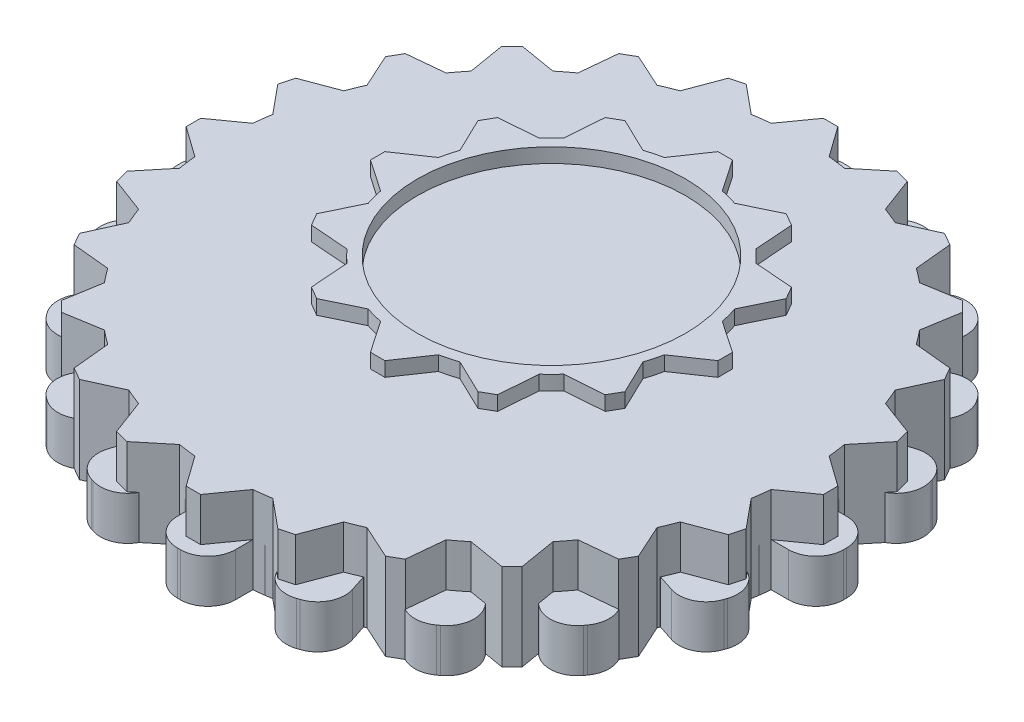
SolidWorks part; units mm, degrees
ref_plane "Front Plane" through (0, 0, 0) normal (0, 0, 1) x (1, 0, 0)
ref_plane "Top Plane" through (0, 0, 0) normal (0, 1, 0) x (1, 0, 0)
ref_plane "Right Plane" through (0, 0, 0) normal (1, 0, 0) x (0, 0, -1)
sketch "Sketch1" plane through (0, 0, 0) normal (0, 1, 0) x (1, 0, 0)
  line L86 (-2.6424, 4.8669) -> (1.3576, 4.8669)
  line L111 (-1.1424, 15.3669) -> (-0.1424, 15.3669)
  line L112 (-0.1424, 15.3669) -> (1.3576, 13.1649)
  line L113 (-1.1424, 15.3669) -> (-2.6424, 13.1649)
  line L114 (5.7906, 13.5092) -> (5.9886, 10.8522)
  line L115 (4.9246, 14.0092) -> (5.7906, 13.5092)
  line L116 (4.9246, 14.0092) -> (2.5245, 12.8522)
  line L117 (9.9999, 8.9339) -> (8.8429, 6.5338)
  line L118 (9.4999, 9.7999) -> (9.9999, 8.9339)
  line L119 (9.4999, 9.7999) -> (6.8429, 9.9979)
  line L120 (11.3576, 2.8669) -> (9.1556, 1.3669)
  line L121 (11.3576, 3.8669) -> (11.3576, 2.8669)
  line L122 (11.3576, 3.8669) -> (9.1556, 5.3669)
  line L123 (9.4999, -3.0661) -> (6.8429, -3.2641)
  line L124 (9.9999, -2.2001) -> (9.4999, -3.0661)
  line L125 (9.9999, -2.2001) -> (8.8429, 0.2)
  line L126 (4.9246, -7.2754) -> (2.5245, -6.1184)
  line L127 (5.7906, -6.7754) -> (4.9246, -7.2754)
  line L128 (5.7906, -6.7754) -> (5.9886, -4.1184)
  line L129 (-1.1424, -8.6331) -> (-2.6424, -6.4311)
  line L130 (-0.1424, -8.6331) -> (-1.1424, -8.6331)
  line L131 (-0.1424, -8.6331) -> (1.3576, -6.4311)
  line L132 (-7.0754, -6.7754) -> (-7.2734, -4.1184)
  line L133 (-6.2094, -7.2754) -> (-7.0754, -6.7754)
  line L134 (-6.2094, -7.2754) -> (-3.8093, -6.1184)
  line L135 (-11.2847, -2.2001) -> (-10.1277, 0.2)
  line L136 (-10.7847, -3.0661) -> (-11.2847, -2.2001)
  line L137 (-10.7847, -3.0661) -> (-8.1277, -3.2641)
  line L138 (-12.6424, 3.8669) -> (-10.4404, 5.3669)
  line L139 (-12.6424, 2.8669) -> (-12.6424, 3.8669)
  line L140 (-12.6424, 2.8669) -> (-10.4404, 1.3669)
  line L141 (-10.7847, 9.7999) -> (-8.1277, 9.9979)
  line L142 (-11.2847, 8.9339) -> (-10.7847, 9.7999)
  line L143 (-11.2847, 8.9339) -> (-10.1277, 6.5338)
  line L144 (-6.2094, 14.0092) -> (-3.8093, 12.8522)
  line L145 (-7.0754, 13.5092) -> (-6.2094, 14.0092)
  line L146 (-7.0754, 13.5092) -> (-7.2734, 10.8522)
  line L147 (-2.6424, 1.8669) -> (1.3576, 1.8669)
  line L149 (-3.1424, 4.8669) -> (1.8576, 1.8669) construction
  line L150 (-3.1424, 1.8669) -> (1.8576, 4.8669) construction
  arc A43 (-2.6424, 13.1649) -> (-3.8093, 12.8522) centre (-0.6424, 3.3669) ccw
  arc A44 (-7.2734, 10.8522) -> (-8.1277, 9.9979) centre (-0.6424, 3.3669) ccw
  arc A45 (-10.1277, 6.5338) -> (-10.4404, 5.3669) centre (-0.6424, 3.3669) ccw
  arc A46 (-10.4404, 1.3669) -> (-10.1277, 0.2) centre (-0.6424, 3.3669) ccw
  arc A47 (-8.1277, -3.2641) -> (-7.2734, -4.1184) centre (-0.6424, 3.3669) ccw
  arc A48 (-3.8093, -6.1184) -> (-2.6424, -6.4311) centre (-0.6424, 3.3669) ccw
  arc A49 (1.3576, -6.4311) -> (2.5245, -6.1184) centre (-0.6424, 3.3669) ccw
  arc A50 (5.9886, -4.1184) -> (6.8429, -3.2641) centre (-0.6424, 3.3669) ccw
  arc A51 (8.8429, 0.2) -> (9.1556, 1.3669) centre (-0.6424, 3.3669) ccw
  arc A52 (9.1556, 5.3669) -> (8.8429, 6.5338) centre (-0.6424, 3.3669) ccw
  arc A53 (6.8429, 9.9979) -> (5.9886, 10.8522) centre (-0.6424, 3.3669) ccw
  arc A54 (2.5245, 12.8522) -> (1.3576, 13.1649) centre (-0.6424, 3.3669) ccw
  arc A55 (-2.6424, 4.8669) -> (-2.6424, 1.8669) centre (-0.6424, 3.3669) ccw
  arc A56 (1.3576, 1.8669) -> (1.3576, 4.8669) centre (-0.6424, 3.3669) ccw
  point P6 (0, 0)
  point P8 (0, 0)
  point P9 (0, 0)
  point P12 (0, 2.7462)
  point P17 (0, 0)
  point P18 (0, 2.7462)
  point P22 (-2.5, 0.7462)
  point P63 (0, 0)
  point P68 (0, 0)
  point P69 (-0.6424, 3.3669)
  point P119 (0, 0)
  dimension "D1" = 20
  dimension "D2" = 3
  dimension "D3" = 5
  dimension "D8" = 12
sketch "Sketch2" plane through (0, 0, 0) normal (0, 1, 0) x (1, 0, 0)
  line L0 (-2, 0) -> (2, 0)
  line L1 (-23, -0.1) -> (-23, 0.1)
  line L2 (-21.1, 2) -> (-19.8997, 2)
  line L3 (-21.1, -2) -> (-19.8997, -2)
  line L4 (-20.6853, 4.6181) -> (-19.5438, 4.2472)
  line L5 (-19.4493, 8.4224) -> (-18.3078, 8.0515)
  line L6 (-21.9052, 7.0123) -> (-21.8434, 7.2025)
  line L7 (-18.2458, 10.7842) -> (-17.2748, 10.0787)
  line L8 (-15.8947, 14.0203) -> (-14.9237, 13.3148)
  line L9 (-18.6662, 13.4382) -> (-18.5486, 13.6)
  line L10 (-14.0203, 15.8947) -> (-13.3148, 14.9237)
  line L11 (-10.7842, 18.2458) -> (-10.0787, 17.2748)
  line L12 (-13.6, 18.5486) -> (-13.4382, 18.6662)
  line L13 (-8.4224, 19.4493) -> (-8.0515, 18.3078)
  line L14 (-4.6181, 20.6853) -> (-4.2472, 19.5438)
  line L15 (-7.2025, 21.8434) -> (-7.0123, 21.9052)
  line L16 (-2, 21.1) -> (-2, 19.8997)
  line L17 (2, 21.1) -> (2, 19.8997)
  line L18 (-0.1, 23) -> (0.1, 23)
  line L19 (4.6181, 20.6853) -> (4.2472, 19.5438)
  line L20 (8.4224, 19.4493) -> (8.0515, 18.3078)
  line L21 (7.0123, 21.9052) -> (7.2025, 21.8434)
  line L22 (10.7842, 18.2458) -> (10.0787, 17.2748)
  line L23 (14.0203, 15.8947) -> (13.3148, 14.9237)
  line L24 (13.4382, 18.6662) -> (13.6, 18.5486)
  line L25 (15.8947, 14.0203) -> (14.9237, 13.3148)
  line L26 (18.2458, 10.7842) -> (17.2748, 10.0787)
  line L27 (18.5486, 13.6) -> (18.6662, 13.4382)
  line L28 (19.4493, 8.4224) -> (18.3078, 8.0515)
  line L29 (20.6853, 4.6181) -> (19.5438, 4.2472)
  line L30 (21.8434, 7.2025) -> (21.9052, 7.0123)
  line L31 (21.1, 2) -> (19.8997, 2)
  line L32 (21.1, -2) -> (19.8997, -2)
  line L33 (23, 0.1) -> (23, -0.1)
  line L34 (20.6853, -4.6181) -> (19.5438, -4.2472)
  line L35 (19.4493, -8.4224) -> (18.3078, -8.0515)
  line L36 (21.9052, -7.0123) -> (21.8434, -7.2025)
  line L37 (18.2458, -10.7842) -> (17.2748, -10.0787)
  line L38 (15.8947, -14.0203) -> (14.9237, -13.3148)
  line L39 (18.6662, -13.4382) -> (18.5486, -13.6)
  line L40 (14.0203, -15.8947) -> (13.3148, -14.9237)
  line L41 (10.7842, -18.2458) -> (10.0787, -17.2748)
  line L42 (13.6, -18.5486) -> (13.4382, -18.6662)
  line L43 (8.4224, -19.4493) -> (8.0515, -18.3078)
  line L44 (4.6181, -20.6853) -> (4.2472, -19.5438)
  line L45 (7.2025, -21.8434) -> (7.0123, -21.9052)
  line L46 (2, -21.1) -> (2, -19.8997)
  line L47 (-2, -21.1) -> (-2, -19.8997)
  line L48 (0.1, -23) -> (-0.1, -23)
  line L49 (-4.6181, -20.6853) -> (-4.2472, -19.5438)
  line L50 (-8.4224, -19.4493) -> (-8.0515, -18.3078)
  line L51 (-7.0123, -21.9052) -> (-7.2025, -21.8434)
  line L52 (-10.7842, -18.2458) -> (-10.0787, -17.2748)
  line L53 (-14.0203, -15.8947) -> (-13.3148, -14.9237)
  line L54 (-13.4382, -18.6662) -> (-13.6, -18.5486)
  line L55 (-15.8947, -14.0203) -> (-14.9237, -13.3148)
  line L56 (-18.2458, -10.7842) -> (-17.2748, -10.0787)
  line L57 (-18.5486, -13.6) -> (-18.6662, -13.4382)
  line L58 (-19.4493, -8.4224) -> (-18.3078, -8.0515)
  line L59 (-20.6853, -4.6181) -> (-19.5438, -4.2472)
  line L60 (-21.8434, -7.2025) -> (-21.9052, -7.0123)
  arc A0 (-18.3078, -8.0515) -> (-17.2748, -10.0787) centre (0, 0) ccw
  arc A1 (-21.1, 2) -> (-23, 0.1) centre (-21.1, 0.1) ccw
  arc A2 (-21.1, -2) -> (-23, -0.1) centre (-21.1, -0.1) cw
  arc A3 (-20.6853, 4.6181) -> (-21.9052, 7.0123) centre (-20.0982, 6.4252) cw
  arc A4 (-19.4493, 8.4224) -> (-21.8434, 7.2025) centre (-20.0364, 6.6154) ccw
  arc A5 (-18.2458, 10.7842) -> (-18.6662, 13.4382) centre (-17.129, 12.3214) cw
  arc A6 (-15.8947, 14.0203) -> (-18.5486, 13.6) centre (-17.0115, 12.4832) ccw
  arc A7 (-14.0203, 15.8947) -> (-13.6, 18.5486) centre (-12.4832, 17.0115) cw
  arc A8 (-10.7842, 18.2458) -> (-13.4382, 18.6662) centre (-12.3214, 17.129) ccw
  arc A9 (-8.4224, 19.4493) -> (-7.2025, 21.8434) centre (-6.6154, 20.0364) cw
  arc A10 (-4.6181, 20.6853) -> (-7.0123, 21.9052) centre (-6.4252, 20.0982) ccw
  arc A11 (-2, 21.1) -> (-0.1, 23) centre (-0.1, 21.1) cw
  arc A12 (2, 21.1) -> (0.1, 23) centre (0.1, 21.1) ccw
  arc A13 (4.6181, 20.6853) -> (7.0123, 21.9052) centre (6.4252, 20.0982) cw
  arc A14 (8.4224, 19.4493) -> (7.2025, 21.8434) centre (6.6154, 20.0364) ccw
  arc A15 (10.7842, 18.2458) -> (13.4382, 18.6662) centre (12.3214, 17.129) cw
  arc A16 (14.0203, 15.8947) -> (13.6, 18.5486) centre (12.4832, 17.0115) ccw
  arc A17 (15.8947, 14.0203) -> (18.5486, 13.6) centre (17.0115, 12.4832) cw
  arc A18 (18.2458, 10.7842) -> (18.6662, 13.4382) centre (17.129, 12.3214) ccw
  arc A19 (19.4493, 8.4224) -> (21.8434, 7.2025) centre (20.0364, 6.6154) cw
  arc A20 (20.6853, 4.6181) -> (21.9052, 7.0123) centre (20.0982, 6.4252) ccw
  arc A21 (21.1, 2) -> (23, 0.1) centre (21.1, 0.1) cw
  arc A22 (21.1, -2) -> (23, -0.1) centre (21.1, -0.1) ccw
  arc A23 (20.6853, -4.6181) -> (21.9052, -7.0123) centre (20.0982, -6.4252) cw
  arc A24 (19.4493, -8.4224) -> (21.8434, -7.2025) centre (20.0364, -6.6154) ccw
  arc A25 (18.2458, -10.7842) -> (18.6662, -13.4382) centre (17.129, -12.3214) cw
  arc A26 (15.8947, -14.0203) -> (18.5486, -13.6) centre (17.0115, -12.4832) ccw
  arc A27 (14.0203, -15.8947) -> (13.6, -18.5486) centre (12.4832, -17.0115) cw
  arc A28 (10.7842, -18.2458) -> (13.4382, -18.6662) centre (12.3214, -17.129) ccw
  arc A29 (8.4224, -19.4493) -> (7.2025, -21.8434) centre (6.6154, -20.0364) cw
  arc A30 (4.6181, -20.6853) -> (7.0123, -21.9052) centre (6.4252, -20.0982) ccw
  arc A31 (2, -21.1) -> (0.1, -23) centre (0.1, -21.1) cw
  arc A32 (-2, -21.1) -> (-0.1, -23) centre (-0.1, -21.1) ccw
  arc A33 (-4.6181, -20.6853) -> (-7.0123, -21.9052) centre (-6.4252, -20.0982) cw
  arc A34 (-8.4224, -19.4493) -> (-7.2025, -21.8434) centre (-6.6154, -20.0364) ccw
  arc A35 (-10.7842, -18.2458) -> (-13.4382, -18.6662) centre (-12.3214, -17.129) cw
  arc A36 (-14.0203, -15.8947) -> (-13.6, -18.5486) centre (-12.4832, -17.0115) ccw
  arc A37 (-15.8947, -14.0203) -> (-18.5486, -13.6) centre (-17.0115, -12.4832) cw
  arc A38 (-18.2458, -10.7842) -> (-18.6662, -13.4382) centre (-17.129, -12.3214) ccw
  arc A39 (-19.4493, -8.4224) -> (-21.8434, -7.2025) centre (-20.0364, -6.6154) cw
  arc A40 (-20.6853, -4.6181) -> (-21.9052, -7.0123) centre (-20.0982, -6.4252) ccw
  arc A41 (-19.8997, -2) -> (-19.5438, -4.2472) centre (0, 0) ccw
  arc A42 (-19.5438, 4.2472) -> (-19.8997, 2) centre (0, 0) ccw
  arc A43 (-17.2748, 10.0787) -> (-18.3078, 8.0515) centre (0, 0) ccw
  arc A44 (-13.3148, 14.9237) -> (-14.9237, 13.3148) centre (0, 0) ccw
  arc A45 (-8.0515, 18.3078) -> (-10.0787, 17.2748) centre (0, 0) ccw
  arc A46 (-2, 19.8997) -> (-4.2472, 19.5438) centre (0, 0) ccw
  arc A47 (4.2472, 19.5438) -> (2, 19.8997) centre (0, 0) ccw
  arc A48 (10.0787, 17.2748) -> (8.0515, 18.3078) centre (0, 0) ccw
  arc A49 (14.9237, 13.3148) -> (13.3148, 14.9237) centre (0, 0) ccw
  arc A50 (18.3078, 8.0515) -> (17.2748, 10.0787) centre (0, 0) ccw
  arc A51 (19.8997, 2) -> (19.5438, 4.2472) centre (0, 0) ccw
  arc A52 (19.5438, -4.2472) -> (19.8997, -2) centre (0, 0) ccw
  arc A53 (17.2748, -10.0787) -> (18.3078, -8.0515) centre (0, 0) ccw
  arc A54 (13.3148, -14.9237) -> (14.9237, -13.3148) centre (0, 0) ccw
  arc A55 (8.0515, -18.3078) -> (10.0787, -17.2748) centre (0, 0) ccw
  arc A56 (2, -19.8997) -> (4.2472, -19.5438) centre (0, 0) ccw
  arc A57 (-10.0787, -17.2748) -> (-8.0515, -18.3078) centre (0, 0) ccw
  arc A58 (-4.2472, -19.5438) -> (-2, -19.8997) centre (0, 0) ccw
  arc A59 (-14.9237, -13.3148) -> (-13.3148, -14.9237) centre (0, 0) ccw
  point P6 (0, 0)
  point P10 (-23, 2)
  point P170 (0, 0)
  dimension "D1" = 40
  dimension "D4" = 1.9
  dimension "D5" = 20
extrude "Boss-Extrude3" add sketch "Sketch2" along normal blind 3 contours L55 A59 L53 A36 L54 A35 L52 A57 L50 A34 L51 A33 L49 A58 L47 A32 L48 A31 L46 A56 L44 A30 L45 A29 L43 A55 L41 A28 L42 A27 L40 A54 L38 A26 L39 A25 L37 A53 L35 A24 L36 A23 L34 A52 L32 A22 L33 A21 region at (-22.3495, 0, 0)
sketch "Sketch3" plane through (0, 0, 0) normal (0, 1, 0) x (1, 0, 0)
  line L0 (-22, 0) -> (22, 0)
  line L1 (22, -0.5) -> (22, 0.5)
  line L2 (22, 0.5) -> (19.8997, 2)
  line L3 (22, -0.5) -> (19.8997, -2)
  line L4 (21.3798, -5.2111) -> (19.7393, -3.2186)
  line L5 (21.121, -6.177) -> (21.3798, -5.2111)
  line L6 (21.121, -6.177) -> (18.704, -7.0823)
  line L7 (19.3026, -10.567) -> (18.2337, -8.2178)
  line L8 (18.8026, -11.433) -> (19.3026, -10.567)
  line L9 (18.8026, -11.433) -> (16.2337, -11.6819)
  line L10 (15.9099, -15.2028) -> (15.4855, -12.657)
  line L11 (15.2028, -15.9099) -> (15.9099, -15.2028)
  line L12 (15.2028, -15.9099) -> (12.657, -15.4855)
  line L13 (11.433, -18.8026) -> (11.6819, -16.2337)
  line L14 (10.567, -19.3026) -> (11.433, -18.8026)
  line L15 (10.567, -19.3026) -> (8.2178, -18.2337)
  line L16 (6.177, -21.121) -> (7.0823, -18.704)
  line L17 (5.2111, -21.3798) -> (6.177, -21.121)
  line L18 (5.2111, -21.3798) -> (3.2186, -19.7393)
  line L19 (0.5, -22) -> (2, -19.8997)
  line L20 (-0.5, -22) -> (0.5, -22)
  line L21 (-0.5, -22) -> (-2, -19.8997)
  line L22 (-5.2111, -21.3798) -> (-3.2186, -19.7393)
  line L23 (-6.177, -21.121) -> (-5.2111, -21.3798)
  line L24 (-6.177, -21.121) -> (-7.0823, -18.704)
  line L25 (-10.567, -19.3026) -> (-8.2178, -18.2337)
  line L26 (-11.433, -18.8026) -> (-10.567, -19.3026)
  line L27 (-11.433, -18.8026) -> (-11.6819, -16.2337)
  line L28 (-15.2028, -15.9099) -> (-12.657, -15.4855)
  line L29 (-15.9099, -15.2028) -> (-15.2028, -15.9099)
  line L30 (-15.9099, -15.2028) -> (-15.4855, -12.657)
  line L31 (-18.8026, -11.433) -> (-16.2337, -11.6819)
  line L32 (-19.3026, -10.567) -> (-18.8026, -11.433)
  line L33 (-19.3026, -10.567) -> (-18.2337, -8.2178)
  line L34 (-21.121, -6.177) -> (-18.704, -7.0823)
  line L35 (-21.3798, -5.2111) -> (-21.121, -6.177)
  line L36 (-21.3798, -5.2111) -> (-19.7393, -3.2186)
  line L37 (-22, -0.5) -> (-19.8997, -2)
  line L38 (-22, 0.5) -> (-22, -0.5)
  line L39 (-22, 0.5) -> (-19.8997, 2)
  line L40 (-21.3798, 5.2111) -> (-19.7393, 3.2186)
  line L41 (-21.121, 6.177) -> (-21.3798, 5.2111)
  line L42 (-21.121, 6.177) -> (-18.704, 7.0823)
  line L43 (-19.3026, 10.567) -> (-18.2337, 8.2178)
  line L44 (-18.8026, 11.433) -> (-19.3026, 10.567)
  line L45 (-18.8026, 11.433) -> (-16.2337, 11.6819)
  line L46 (-15.9099, 15.2028) -> (-15.4855, 12.657)
  line L47 (-15.2028, 15.9099) -> (-15.9099, 15.2028)
  line L48 (-15.2028, 15.9099) -> (-12.657, 15.4855)
  line L49 (-11.433, 18.8026) -> (-11.6819, 16.2337)
  line L50 (-10.567, 19.3026) -> (-11.433, 18.8026)
  line L51 (-10.567, 19.3026) -> (-8.2178, 18.2337)
  line L52 (-6.177, 21.121) -> (-7.0823, 18.704)
  line L53 (-5.2111, 21.3798) -> (-6.177, 21.121)
  line L54 (-5.2111, 21.3798) -> (-3.2186, 19.7393)
  line L55 (-0.5, 22) -> (-2, 19.8997)
  line L56 (0.5, 22) -> (-0.5, 22)
  line L57 (0.5, 22) -> (2, 19.8997)
  line L58 (5.2111, 21.3798) -> (3.2186, 19.7393)
  line L59 (6.177, 21.121) -> (5.2111, 21.3798)
  line L60 (6.177, 21.121) -> (7.0823, 18.704)
  line L61 (10.567, 19.3026) -> (8.2178, 18.2337)
  line L62 (11.433, 18.8026) -> (10.567, 19.3026)
  line L63 (11.433, 18.8026) -> (11.6819, 16.2337)
  line L64 (15.2028, 15.9099) -> (12.657, 15.4855)
  line L65 (15.9099, 15.2028) -> (15.2028, 15.9099)
  line L66 (15.9099, 15.2028) -> (15.4855, 12.657)
  line L67 (18.8026, 11.433) -> (16.2337, 11.6819)
  line L68 (19.3026, 10.567) -> (18.8026, 11.433)
  line L69 (19.3026, 10.567) -> (18.2337, 8.2178)
  line L70 (21.121, 6.177) -> (18.704, 7.0823)
  line L71 (21.3798, 5.2111) -> (21.121, 6.177)
  line L72 (21.3798, 5.2111) -> (19.7393, 3.2186)
  arc A0 (-8.2178, -18.2337) -> (-7.0823, -18.704) centre (0, 0) ccw
  arc A1 (-12.657, -15.4855) -> (-11.6819, -16.2337) centre (0, 0) ccw
  arc A2 (-16.2337, -11.6819) -> (-15.4855, -12.657) centre (0, 0) ccw
  arc A3 (-18.704, -7.0823) -> (-18.2337, -8.2178) centre (0, 0) ccw
  arc A4 (-19.8997, -2) -> (-19.7393, -3.2186) centre (0, 0) ccw
  arc A5 (-19.7393, 3.2186) -> (-19.8997, 2) centre (0, 0) ccw
  arc A6 (-18.2337, 8.2178) -> (-18.704, 7.0823) centre (0, 0) ccw
  arc A7 (-15.4855, 12.657) -> (-16.2337, 11.6819) centre (0, 0) ccw
  arc A8 (-11.6819, 16.2337) -> (-12.657, 15.4855) centre (0, 0) ccw
  arc A9 (-7.0823, 18.704) -> (-8.2178, 18.2337) centre (0, 0) ccw
  arc A10 (-2, 19.8997) -> (-3.2186, 19.7393) centre (0, 0) ccw
  arc A11 (3.2186, 19.7393) -> (2, 19.8997) centre (0, 0) ccw
  arc A12 (8.2178, 18.2337) -> (7.0823, 18.704) centre (0, 0) ccw
  arc A13 (12.657, 15.4855) -> (11.6819, 16.2337) centre (0, 0) ccw
  arc A14 (16.2337, 11.6819) -> (15.4855, 12.657) centre (0, 0) ccw
  arc A15 (18.704, 7.0823) -> (18.2337, 8.2178) centre (0, 0) ccw
  arc A16 (19.8997, 2) -> (19.7393, 3.2186) centre (0, 0) ccw
  arc A17 (19.7393, -3.2186) -> (19.8997, -2) centre (0, 0) ccw
  arc A18 (18.2337, -8.2178) -> (18.704, -7.0823) centre (0, 0) ccw
  arc A19 (-3.2186, -19.7393) -> (-2, -19.8997) centre (0, 0) ccw
  arc A20 (2, -19.8997) -> (3.2186, -19.7393) centre (0, 0) ccw
  arc A21 (7.0823, -18.704) -> (8.2178, -18.2337) centre (0, 0) ccw
  arc A22 (11.6819, -16.2337) -> (12.657, -15.4855) centre (0, 0) ccw
  arc A23 (15.4855, -12.657) -> (16.2337, -11.6819) centre (0, 0) ccw
  point P6 (0, 0)
  point P7 (0, -12.952)
  point P8 (-6.2727, 0)
  point P9 (11.4668, 0)
  point P10 (0, 0)
  point P108 (0, 0)
  dimension "D1" = 40
  dimension "D2" = 22
  dimension "D3" = 2
  dimension "D4" = 24
extrude "Boss-Extrude5" add sketch "Sketch3" along normal blind 6 separate body contours L2 A16 L72 L71 L70 A15 L69 L68 L67 A14 L66 L65 L64 A13 L63 L62 L61 A12 L60 L59 L58 A11 L57 L56 L55 A10 L54 L53 L52 A9 L51 L50 L49 A8 L48 L47 L46 A7 L45 L44 L43 A6 L42 L41 L40 A5 L39 L38 L0 L1 | L10 A23 L9 L8 L7 A18 L6 L5 L4 A17 L3 L1 L0 L38 L37 A4 L36 L35 L34 A3 L33 L32 L31 A2 L30 L29 L28 A1 L27 L26 L25 A0 L24 L23 L22 A19 L21 L20 L19 A20 L18 L17 L16 A21 L15 L14 L13 A22 L12 L11 region at (0, 0, -8.8989) region at (0, 0, 8.8989)
extrude "Boss-Extrude6" add sketch "Sketch1" along normal blind 5.5 separate body
sketch "Sketch5" plane through (0, 5.5, 0) normal (0, 1, 0) x (1, 0, 0)
  line L0 (-0.6424, 15.3669) -> (-0.6424, -8.6331) construction
  line L1 (-0.1424, 15.3669) -> (-1.1424, 15.3669) construction
  line L2 (-1.1424, -8.6331) -> (-0.1424, -8.6331) construction
  line L3 (11.3576, 3.3669) -> (-12.6424, 3.3669) construction
  line L4 (11.3576, 2.8669) -> (11.3576, 3.8669) construction
  line L5 (-12.6424, 3.8669) -> (-12.6424, 2.8669) construction
  circle A0 centre (-0.6424, 3.3669) radius 5.1751
sketch "Sketch6" plane through (0, 5.5, 0) normal (0, 1, 0) x (1, 0, 0)
  line L72 (-1.1424, 15.3669) -> (-2.6424, 13.1649)
  line L73 (-3.8093, 12.8522) -> (-6.2094, 14.0092)
  line L74 (-6.2094, 14.0092) -> (-7.0754, 13.5092)
  line L75 (-7.0754, 13.5092) -> (-7.2734, 10.8522)
  line L76 (-8.1277, 9.9979) -> (-10.7847, 9.7999)
  line L77 (-10.7847, 9.7999) -> (-11.2847, 8.9339)
  line L78 (-11.2847, 8.9339) -> (-10.1277, 6.5338)
  line L79 (-10.4404, 5.3669) -> (-12.6424, 3.8669)
  line L80 (-12.6424, 3.8669) -> (-12.6424, 2.8669)
  line L81 (-12.6424, 2.8669) -> (-10.4404, 1.3669)
  line L82 (-10.1277, 0.2) -> (-11.2847, -2.2001)
  line L83 (-11.2847, -2.2001) -> (-10.7847, -3.0661)
  line L84 (-10.7847, -3.0661) -> (-8.1277, -3.2641)
  line L85 (-7.2734, -4.1184) -> (-7.0754, -6.7754)
  line L86 (-7.0754, -6.7754) -> (-6.2094, -7.2754)
  line L87 (-6.2094, -7.2754) -> (-3.8093, -6.1184)
  line L88 (-2.6424, -6.4311) -> (-1.1424, -8.6331)
  line L89 (-1.1424, -8.6331) -> (-0.1424, -8.6331)
  line L90 (-0.1424, -8.6331) -> (1.3576, -6.4311)
  line L91 (2.5245, -6.1184) -> (4.9246, -7.2754)
  line L92 (4.9246, -7.2754) -> (5.7906, -6.7754)
  line L93 (5.7906, -6.7754) -> (5.9886, -4.1184)
  line L94 (6.8429, -3.2641) -> (9.4999, -3.0661)
  line L95 (9.4999, -3.0661) -> (9.9999, -2.2001)
  line L96 (9.9999, -2.2001) -> (8.8429, 0.2)
  line L97 (9.1556, 1.3669) -> (11.3576, 2.8669)
  line L98 (11.3576, 2.8669) -> (11.3576, 3.8669)
  line L99 (11.3576, 3.8669) -> (9.1556, 5.3669)
  line L100 (8.8429, 6.5338) -> (9.9999, 8.9339)
  line L101 (9.9999, 8.9339) -> (9.4999, 9.7999)
  line L102 (9.4999, 9.7999) -> (6.8429, 9.9979)
  line L103 (5.9886, 10.8522) -> (5.7906, 13.5092)
  line L104 (5.7906, 13.5092) -> (4.9246, 14.0092)
  line L105 (4.9246, 14.0092) -> (2.5245, 12.8522)
  line L106 (1.3576, 13.1649) -> (-0.1424, 15.3669)
  line L107 (-0.1424, 15.3669) -> (-1.1424, 15.3669)
  line L108 (-1.1424, 15.3669) -> (-2.6424, 13.1649)
  line L109 (-3.8093, 12.8522) -> (-6.2094, 14.0092)
  line L110 (-6.2094, 14.0092) -> (-7.0754, 13.5092)
  line L111 (-7.0754, 13.5092) -> (-7.2734, 10.8522)
  line L112 (-8.1277, 9.9979) -> (-10.7847, 9.7999)
  line L113 (-10.7847, 9.7999) -> (-11.2847, 8.9339)
  line L114 (-11.2847, 8.9339) -> (-10.1277, 6.5338)
  line L115 (-10.4404, 5.3669) -> (-12.6424, 3.8669)
  line L116 (-12.6424, 3.8669) -> (-12.6424, 2.8669)
  line L117 (-12.6424, 2.8669) -> (-10.4404, 1.3669)
  line L118 (-10.1277, 0.2) -> (-11.2847, -2.2001)
  line L119 (-11.2847, -2.2001) -> (-10.7847, -3.0661)
  line L120 (-10.7847, -3.0661) -> (-8.1277, -3.2641)
  line L121 (-7.2734, -4.1184) -> (-7.0754, -6.7754)
  line L122 (-7.0754, -6.7754) -> (-6.2094, -7.2754)
  line L123 (-6.2094, -7.2754) -> (-3.8093, -6.1184)
  line L124 (-2.6424, -6.4311) -> (-1.1424, -8.6331)
  line L125 (-1.1424, -8.6331) -> (-0.1424, -8.6331)
  line L126 (-0.1424, -8.6331) -> (1.3576, -6.4311)
  line L127 (2.5245, -6.1184) -> (4.9246, -7.2754)
  line L128 (4.9246, -7.2754) -> (5.7906, -6.7754)
  line L129 (5.7906, -6.7754) -> (5.9886, -4.1184)
  line L130 (6.8429, -3.2641) -> (9.4999, -3.0661)
  line L131 (9.4999, -3.0661) -> (9.9999, -2.2001)
  line L132 (9.9999, -2.2001) -> (8.8429, 0.2)
  line L133 (9.1556, 1.3669) -> (11.3576, 2.8669)
  line L134 (11.3576, 2.8669) -> (11.3576, 3.8669)
  line L135 (11.3576, 3.8669) -> (9.1556, 5.3669)
  line L136 (8.8429, 6.5338) -> (9.9999, 8.9339)
  line L137 (9.9999, 8.9339) -> (9.4999, 9.7999)
  line L138 (9.4999, 9.7999) -> (6.8429, 9.9979)
  line L139 (5.9886, 10.8522) -> (5.7906, 13.5092)
  line L140 (5.7906, 13.5092) -> (4.9246, 14.0092)
  line L141 (4.9246, 14.0092) -> (2.5245, 12.8522)
  line L142 (1.3576, 13.1649) -> (-0.1424, 15.3669)
  line L143 (-0.1424, 15.3669) -> (-1.1424, 15.3669)
  circle A0 centre (-0.6424, 3.3669) radius 9.25
  arc A27 (-2.6424, 13.1649) -> (-3.8093, 12.8522) centre (-0.6424, 3.3669) ccw
  arc A28 (-7.2734, 10.8522) -> (-8.1277, 9.9979) centre (-0.6424, 3.3669) ccw
  arc A29 (-10.1277, 6.5338) -> (-10.4404, 5.3669) centre (-0.6424, 3.3669) ccw
  arc A30 (-10.4404, 1.3669) -> (-10.1277, 0.2) centre (-0.6424, 3.3669) ccw
  arc A31 (-8.1277, -3.2641) -> (-7.2734, -4.1184) centre (-0.6424, 3.3669) ccw
  arc A32 (-3.8093, -6.1184) -> (-2.6424, -6.4311) centre (-0.6424, 3.3669) ccw
  arc A33 (1.3576, -6.4311) -> (2.5245, -6.1184) centre (-0.6424, 3.3669) ccw
  arc A34 (5.9886, -4.1184) -> (6.8429, -3.2641) centre (-0.6424, 3.3669) ccw
  arc A35 (8.8429, 0.2) -> (9.1556, 1.3669) centre (-0.6424, 3.3669) ccw
  arc A36 (9.1556, 5.3669) -> (8.8429, 6.5338) centre (-0.6424, 3.3669) ccw
  arc A37 (6.8429, 9.9979) -> (5.9886, 10.8522) centre (-0.6424, 3.3669) ccw
  arc A38 (2.5245, 12.8522) -> (1.3576, 13.1649) centre (-0.6424, 3.3669) ccw
  arc A39 (-2.6424, 13.1649) -> (-3.8093, 12.8522) centre (-0.6424, 3.3669) ccw
  arc A40 (-7.2734, 10.8522) -> (-8.1277, 9.9979) centre (-0.6424, 3.3669) ccw
  arc A41 (-10.1277, 6.5338) -> (-10.4404, 5.3669) centre (-0.6424, 3.3669) ccw
  arc A42 (-10.4404, 1.3669) -> (-10.1277, 0.2) centre (-0.6424, 3.3669) ccw
  arc A43 (-8.1277, -3.2641) -> (-7.2734, -4.1184) centre (-0.6424, 3.3669) ccw
  arc A44 (-3.8093, -6.1184) -> (-2.6424, -6.4311) centre (-0.6424, 3.3669) ccw
  arc A45 (1.3576, -6.4311) -> (2.5245, -6.1184) centre (-0.6424, 3.3669) ccw
  arc A46 (5.9886, -4.1184) -> (6.8429, -3.2641) centre (-0.6424, 3.3669) ccw
  arc A47 (8.8429, 0.2) -> (9.1556, 1.3669) centre (-0.6424, 3.3669) ccw
  arc A48 (9.1556, 5.3669) -> (8.8429, 6.5338) centre (-0.6424, 3.3669) ccw
  arc A49 (6.8429, 9.9979) -> (5.9886, 10.8522) centre (-0.6424, 3.3669) ccw
  arc A50 (2.5245, 12.8522) -> (1.3576, 13.1649) centre (-0.6424, 3.3669) ccw
  dimension "D1" = 18.5
  dimension "D3" = 0
extrude "Boss-Extrude7" add sketch "Sketch6" along normal blind 1.5
